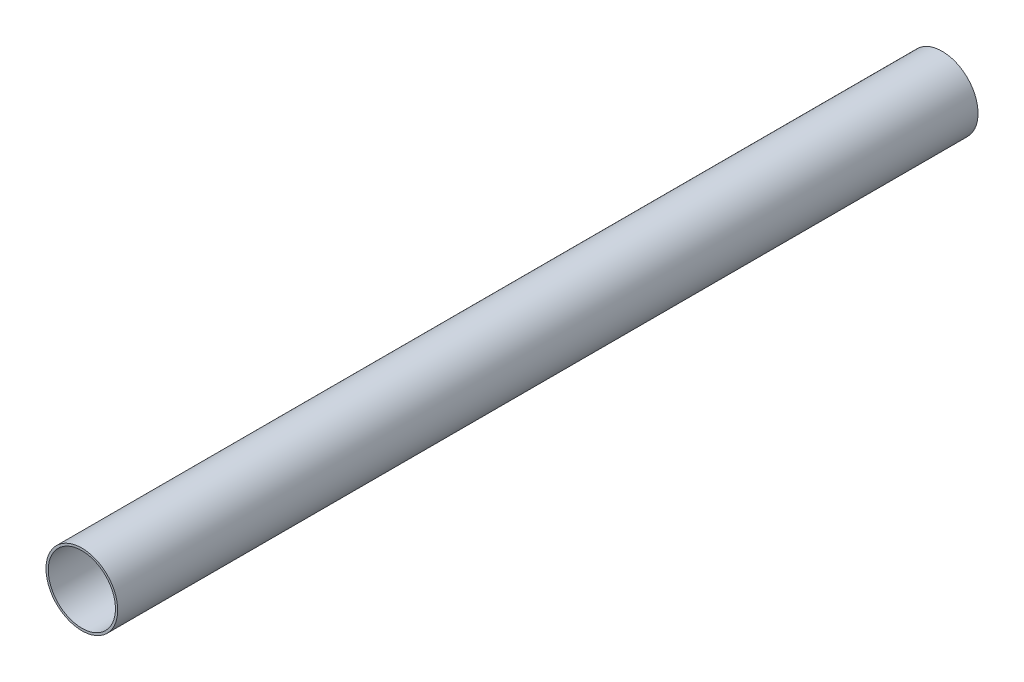
SolidWorks part; units mm, degrees
material "PVC Rigid"
ref_plane "Front Plane" through (0, 0, 0) normal (0, 0, 1) x (1, 0, 0)
ref_plane "Top Plane" through (0, 0, 0) normal (0, 1, 0) x (1, 0, 0)
ref_plane "Right Plane" through (0, 0, 0) normal (1, 0, 0) x (0, 0, -1)
sketch "Sketch1" plane through (0, 0, 0) normal (0, 0, 1) x (1, 0, 0)
  circle A0 centre (0, 0) radius 47.625
  circle A1 centre (0, 0) radius 50.8
  dimension "D1" = 95.25
  dimension "D2" = 101.6
extrude "Boss-Extrude1" add sketch "Sketch1" along normal blind 1219.2
ref_axis "Axis1" through (0, 55.88, 0) along (0, -1, 0)
